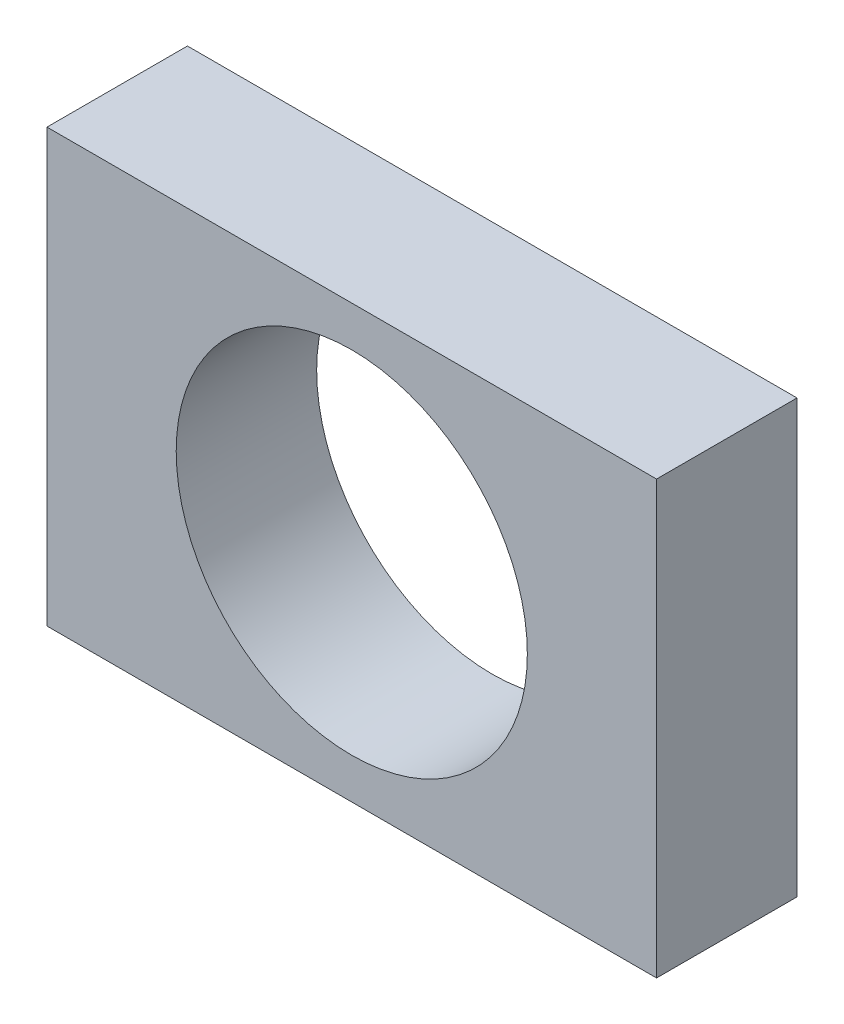
SolidWorks part; units mm, degrees
ref_plane "Front Plane" through (0, 0, 0) normal (0, 0, 1) x (1, 0, 0)
ref_plane "Top Plane" through (0, 0, 0) normal (0, 1, 0) x (1, 0, 0)
ref_plane "Right Plane" through (0, 0, 0) normal (1, 0, 0) x (0, 0, -1)
sketch "Sketch1" plane through (0, 0, 0) normal (0, 0, 1) x (1, 0, 0)
  line L1 (-55.1185, -39.0725) -> (55.1185, -39.0725)
  line L2 (-55.1185, -39.0725) -> (-55.1185, 39.0725)
  line L3 (-55.1185, 39.0725) -> (55.1185, 39.0725)
  line L4 (55.1185, -39.0725) -> (55.1185, 39.0725)
  line L5 (-55.1185, -39.0725) -> (55.1185, 39.0725) construction
  line L6 (-55.1185, 39.0725) -> (55.1185, -39.0725) construction
  point P0 (0, 0)
extrude "Boss-Extrude1" add sketch "Sketch1" against normal blind 25.4
sketch "Sketch2" plane through (0, 0, 0) normal (0, 0, 1) x (1, 0, 0)
  circle A0 centre (0, 0) radius 31.75
  dimension "D1" = 63.5
extrude "Cut-Extrude1" cut sketch "Sketch2" against normal through all
